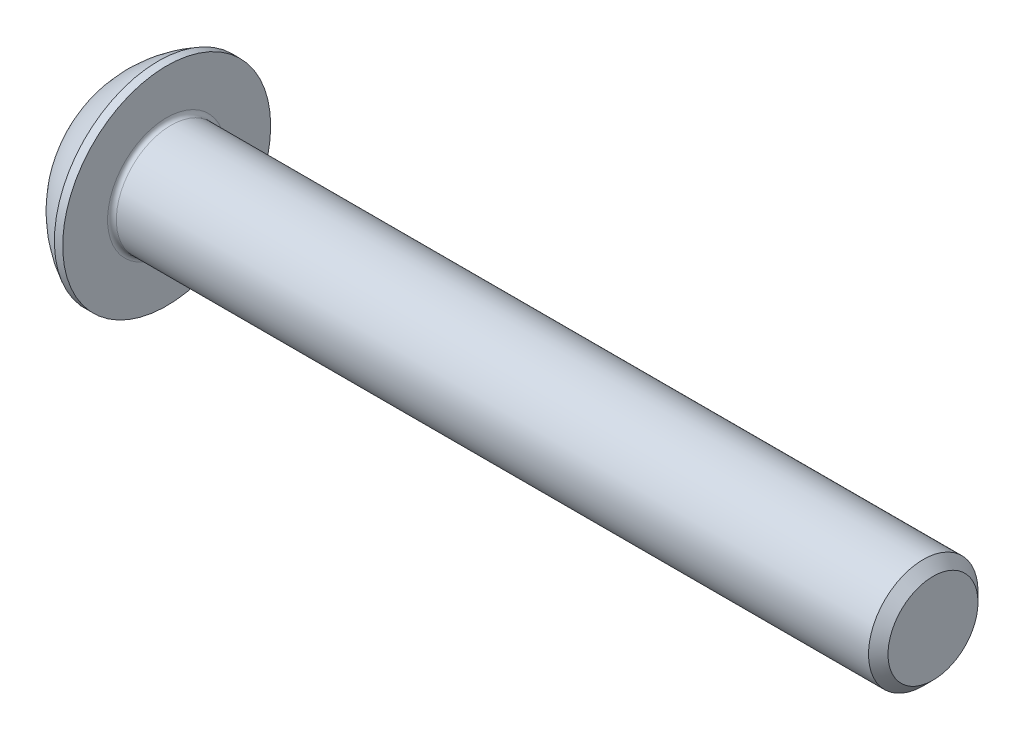
SolidWorks part; units mm, degrees
material "AISI 304"
ref_plane "Спереди" through (0, 0, 0) normal (0, 0, 1) x (1, 0, 0)
ref_plane "Сверху" through (0, 0, 0) normal (0, 1, 0) x (1, 0, 0)
ref_plane "Справа" through (0, 0, 0) normal (1, 0, 0) x (0, 0, -1)
sketch "Эскиз1" plane through (0, 0, 0) normal (0, 0, 1) x (1, 0, 0)
  line L0 (-3.6435, 0) -> (-10.508, 0) construction
  line L1 (0, 2.375) -> (0, 0)
  line L2 (0, 0) -> (37.75, 0)
  line L3 (37.75, 0) -> (37.75, 2.055)
  line L4 (37.75, 2.055) -> (37.305, 2.5)
  line L5 (37.305, 2.5) -> (2.75, 2.5)
  line L6 (2.75, 2.5) -> (2.75, 4.75)
  line L7 (2.75, 4.75) -> (2.3702, 4.75)
  arc A0 (2.3702, 4.75) -> (0, 2.375) centre (4.7549, 0) ccw
  dimension "D1" = 10.63
  dimension "D2" = 4.75
  dimension "D3" = 2.75
  dimension "D4" = 5
  dimension "D5" = 45
  dimension "D6" = 4.11
  dimension "D7" = 35
  dimension "D8" = 9.5
revolve "Body" add sketch "Эскиз1" angle 360 about L0
fillet "Скругление1" radius 0.2 1 edges at (2.75, 0, -2.5)
sketch "Эскиз2" plane through (0, 0, 0) normal (0, 0, 1) x (1, 0, 0)
  line L0 (0, 0) -> (0, 1.5)
  line L1 (0, 2.375) -> (0, -2.375) construction
  line L2 (0, 1.5) -> (1.56, 1.5)
  line L3 (1.56, 1.5) -> (2.426, 0)
  line L4 (2.426, 0) -> (0, 0)
  dimension "D1" = 1.56
  dimension "D2" = 60
  dimension "D3" = 1.5
revolve "Вырез-Повернуть1" cut sketch "Эскиз2" angle 360 about L4
sketch "Эскиз3" plane through (0, 0, 0) normal (-1, 0, 0) x (0, 0, 1)
  line L1 (-1.5, -0.866) -> (0, -1.7321)
  line L2 (0, -1.7321) -> (1.5, -0.866)
  line L3 (1.5, -0.866) -> (1.5, 0.866)
  line L4 (1.5, 0.866) -> (0, 1.7321)
  line L5 (0, 1.7321) -> (-1.5, 0.866)
  line L6 (-1.5, 0.866) -> (-1.5, -0.866)
  circle A0 centre (0, 0) radius 1.5 construction
  dimension "D1" = 3
extrude "Hex" cut sketch "Эскиз3" against normal blind 1.56
